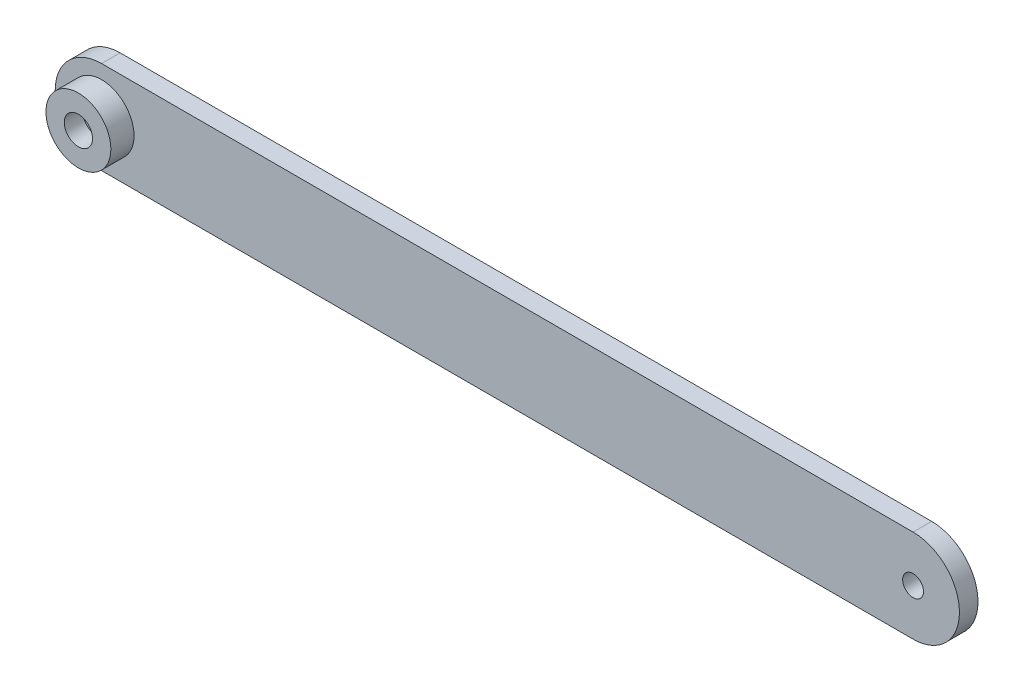
SolidWorks part; units mm, degrees
material "PET"
ref_plane "Front Plane" through (0, 0, 0) normal (0, 0, 1) x (1, 0, 0)
ref_plane "Top Plane" through (0, 0, 0) normal (0, 1, 0) x (1, 0, 0)
ref_plane "Right Plane" through (0, 0, 0) normal (1, 0, 0) x (0, 0, -1)
sketch "Sketch1" plane through (0, 0, 0) normal (0, 0, 1) x (1, 0, 0)
  line L0 (0, 0) -> (175, 0) construction
  line L1 (0, 10) -> (175, 10)
  line L2 (0, -10) -> (175, -10)
  arc A0 (0, 10) -> (0, -10) centre (0, 0) ccw
  arc A1 (175, -10) -> (175, 10) centre (175, 0) ccw
  circle A3 centre (175, 0) radius 2.25
  circle A9 centre (0, 0) radius 1
  point P3 (87.5, 0)
  dimension "D1" = 10
  dimension "D3" = 4.5
  dimension "D4" = 2
  dimension "D2" = 175
extrude "Boss-Extrude1" add sketch "Sketch1" along normal mid plane 4
sketch "Sketch2" plane through (0, 0, -2) normal (0, 0, -1) x (-1, 0, 0)
  circle A0 centre (0, 0) radius 2.5
  dimension "D1" = 5
extrude "Cut-Extrude1" cut sketch "Sketch2" against normal blind 3
sketch "Sketch4" plane through (0, 0, 2) normal (0, 0, 1) x (1, 0, 0)
  circle A0 centre (0, 0) radius 7
  circle A1 centre (0, 0) radius 1 construction
  circle A2 centre (0, 0) radius 1
  dimension "D1" = 14
extrude "Boss-Extrude2" add sketch "Sketch4" along normal blind 1
sketch "Sketch5" plane through (0, 0, 3) normal (0, 0, 1) x (1, 0, 0)
  circle A0 centre (0, 0) radius 7 construction
  circle A1 centre (0, 0) radius 7
  circle A2 centre (0, 0) radius 3.05
  dimension "D1" = 6.1
extrude "Boss-Extrude3" add sketch "Sketch5" along normal blind 4
sketch "Sketch6" plane through (0, 0, -2) normal (0, 0, -1) x (-1, 0, 0)
  line L0 (0, 0) -> (2.5, 0) construction
  line L1 (0, 0) -> (2.4721, 0.3726) construction
  line L2 (2.4721, 0.3726) -> (2.15, 0)
  line L3 (2.15, 0) -> (2.4721, -0.3726)
  circle A0 centre (0, 0) radius 2.5 construction
  arc A1 (2.4721, -0.3726) -> (2.4721, 0.3726) centre (0, 0) ccw
  dimension "D1" = 0.35
  dimension "D2" = 8.571
extrude "Boss-Extrude4" add sketch "Sketch6" against normal blind 3.2
pattern_circular "CirPattern2" count 21 over 360 about axis through (0, 0, 1) along (0, 0, -1) of "Boss-Extrude4" reverse direction yes
